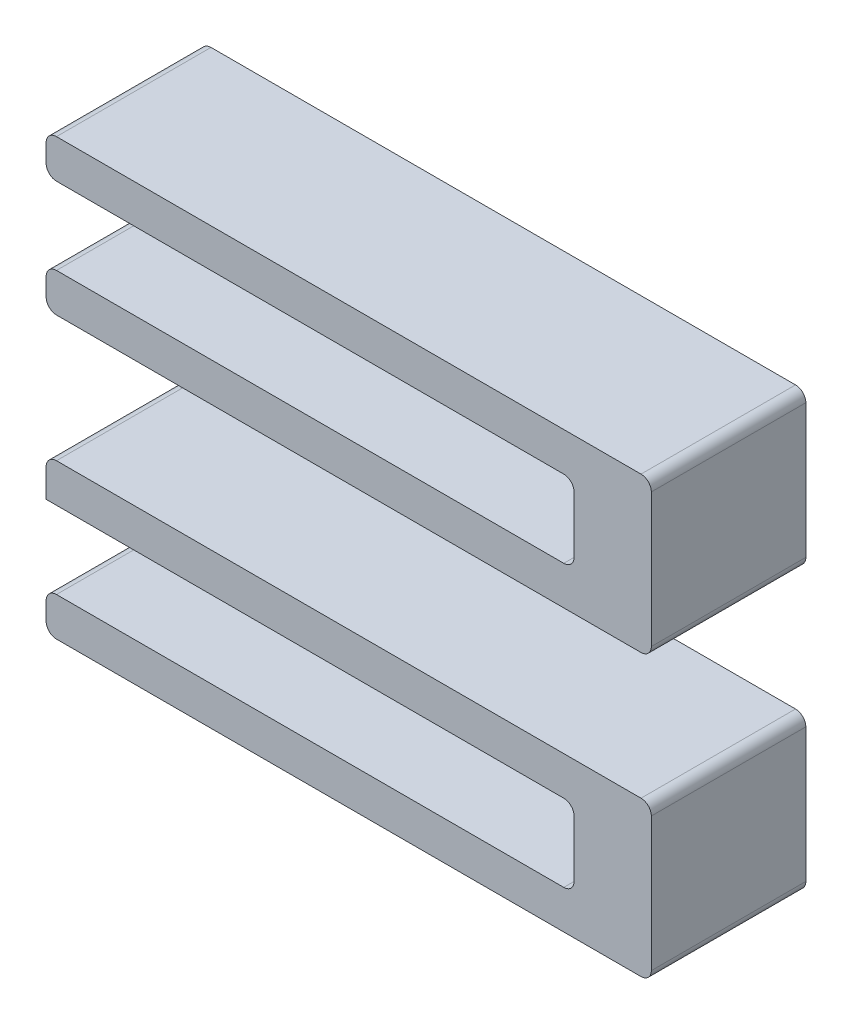
SolidWorks part; units mm, degrees
ref_plane "Front Plane" through (0, 0, 0) normal (0, 0, 1) x (1, 0, 0)
ref_plane "Top Plane" through (0, 0, 0) normal (0, 1, 0) x (1, 0, 0)
ref_plane "Right Plane" through (0, 0, 0) normal (1, 0, 0) x (0, 0, -1)
sketch "Sketch2" plane through (0, 0, 0) normal (0, 0, 1) x (1, 0, 0)
  line L0 (-2.7742, -2.4497) -> (31.3823, -2.4497) construction
  line L1 (0, 0) -> (23.5, 0)
  line L2 (0, 0) -> (0, 6)
  line L3 (0, 6) -> (23.5, 6)
  line L4 (23.5, 0) -> (23.5, 6)
  line L5 (0, 4.5) -> (20.5, 4.5)
  line L6 (0, 4.5) -> (0, 1.5)
  line L7 (0, 1.5) -> (20.5, 1.5)
  line L8 (20.5, 4.5) -> (20.5, 1.5)
  line L9 (0, 4.5) -> (20.5, 4.5)
  line L10 (0, 4.5) -> (0, 3.8)
  line L11 (0, 3.8) -> (20.5, 3.8)
  line L12 (20.5, 4.5) -> (20.5, 3.8)
  line L13 (20.5, -9.3995) -> (20.5, -8.6995)
  line L14 (0, -8.6995) -> (20.5, -8.6995)
  line L15 (0, -9.3995) -> (0, -8.6995)
  line L16 (0, -9.3995) -> (20.5, -9.3995)
  line L17 (20.5, -9.3995) -> (20.5, -6.3995)
  line L18 (0, -6.3995) -> (20.5, -6.3995)
  line L19 (0, -9.3995) -> (0, -6.3995)
  line L20 (0, -9.3995) -> (20.5, -9.3995)
  line L21 (23.5, -4.8995) -> (23.5, -10.8995)
  line L22 (0, -10.8995) -> (23.5, -10.8995)
  line L23 (0, -4.8995) -> (0, -10.8995)
  line L24 (0, -4.8995) -> (23.5, -4.8995)
  dimension "D1" = 6
  dimension "D2" = 3
  dimension "D3" = 1.5
  dimension "D4" = 3
  dimension "D5" = 20.5
  dimension "D6" = 2.3
extrude "Boss-Extrude1" add sketch "Sketch2" along normal blind 6 contours L5 L8 L7 L2 L1 L4 L3 | L24 L23 L18 L17 L13 L16 L22 L21 region at (0.2425, 0.75, 0) region at (20.7425, -9.0495, 0)
extrude "Boss-Extrude3" add sketch "Sketch2<4>" along normal blind 1.2 contours L15 L16 L13 L14 | L6 L11 L8 L5 region at (10.25, 4.15, 0) region at (10.25, -9.0495, 0)
sketch "Sketch2<4>" plane through (0, 0, 0) normal (0, 0, 1) x (1, 0, 0) same geometry as "Sketch2"
fillet "Fillet2" radius 0.4 10 edges at (0, 4.5, 3.6) (20.5, 1.5, 3) (20.5, 3.8, 0.6) (20.5, 4.5, 3.6) (23.5, 6, 3) (23.5, 0, 3) (0, 0, 3) (0, 1.5, 3) (0, 3.8, 0.6) (0, 6, 3)
fillet "Fillet3" radius 0.4 9 edges at (23.5, -10.8995, 3) (23.5, -4.8995, 3) (20.5, -6.3995, 3) (20.5, -9.3995, 3.6) (20.5, -8.6995, 0.6) (0, -10.8995, 3) (0, -9.3995, 3.6) (0, -8.6995, 0.6) (0, -4.8995, 3)
